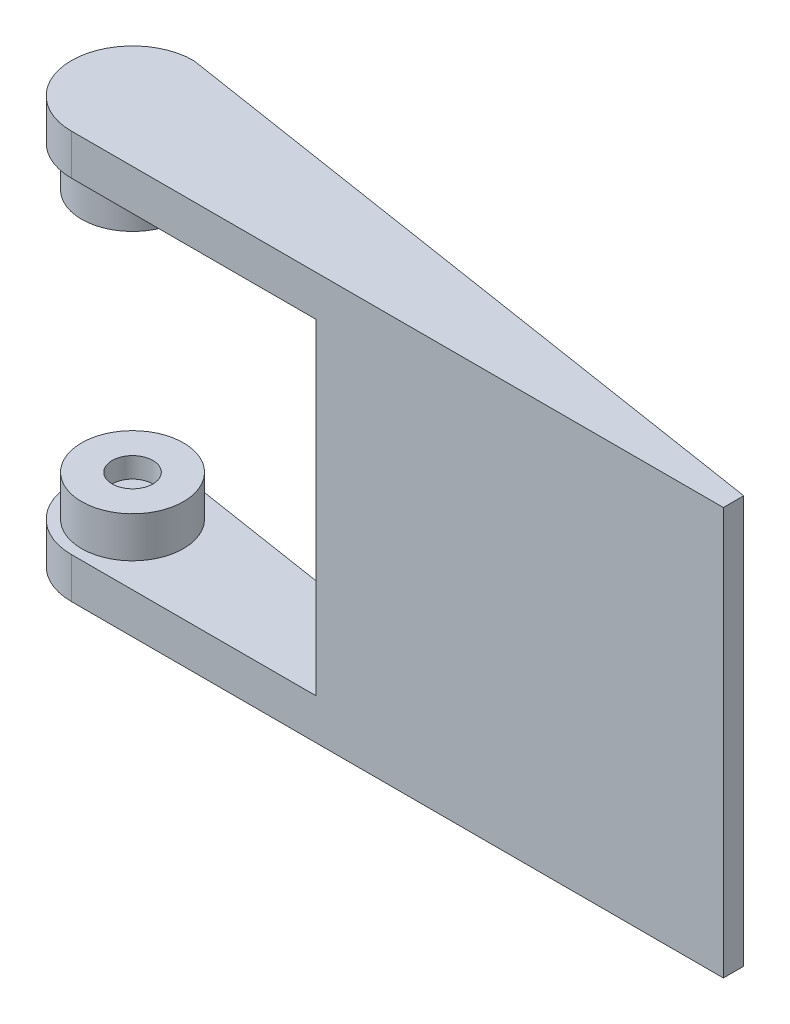
SolidWorks part; units mm, degrees
ref_plane "Front Plane" through (0, 0, 0) normal (0, 0, 1) x (1, 0, 0)
ref_plane "Top Plane" through (0, 0, 0) normal (0, 1, 0) x (1, 0, 0)
ref_plane "Right Plane" through (0, 0, 0) normal (1, 0, 0) x (0, 0, -1)
sketch "Sketch1" plane through (0, 0, 0) normal (0, 1, 0) x (1, 0, 0)
  line L0 (0, 15) -> (160, -10)
  line L1 (0, 15) -> (160, 15)
  line L2 (0, 15) -> (0, -15)
  line L3 (0, -15) -> (160, -15)
  line L4 (160, 15) -> (160, -15)
  circle A0 centre (0, 0) radius 15
  dimension "D1" = 30
  dimension "D2" = 160
  dimension "D3" = 30
  dimension "D4" = 5
extrude "Boss-Extrude1" add sketch "Sketch1" along normal blind 50 contours L2 A0 | L2 A0 L0 | A0 L3 L4 L0 region at (6.3726, 0, 0.0232) region at (-6.3662, 0, 0) region at (68.8227, 0, 5.4452)
sketch "Sketch2" plane through (0, 50, 0) normal (0, 1, 0) x (1, 0, 0)
  line L0 (0, -15) -> (160, -15)
  line L1 (160, -15) -> (160, -10)
  line L2 (160, -10) -> (0, 15)
  line L3 (60, -15) -> (60, 5.625)
  circle A0 centre (0, 0) radius 15
  circle A1 centre (0, 0) radius 12.5
  arc M4 (0, 15) -> (0, -15) centre (0, 0) ccw
  line M5 (0, -15) -> (160, -15)
  line M7 (160, -10) -> (0, 15)
  dimension "D1" = 30
  dimension "D4" = 25
  dimension "D2" = 15
  dimension "D3" = 100
extrude "Cut-Extrude1" cut sketch "Sketch2" against normal blind 40 contours A0 L3 L2 M5 | A0 A1 M4 M7 region at (34.7389, 50, 2.8576) region at (-14.5757, 50, 0)
ref_plane "Plane1" through (0, 50, 0) normal (0, 1, 0) x (1, 0, 0)
sketch "Sketch3" plane through (0, 50, 0) normal (0, 1, 0) x (1, 0, 0)
  circle A0 centre (0, 0) radius 12.5
  dimension "D1" = 25
extrude "Cut-Extrude2" cut sketch "Sketch3" against normal blind 30
sketch "Sketch4" plane through (0, 20, 0) normal (0, 1, 0) x (1, 0, 0)
  circle A0 centre (0, 0) radius 5
  dimension "D1" = 10
extrude "Cut-Extrude3" cut sketch "Sketch4" against normal blind 5
mirror "Mirror1" about plane through (0, 50, 0) normal (0, 1, 0) of "Cut-Extrude3", "Cut-Extrude2", "Boss-Extrude1", "Cut-Extrude1"
